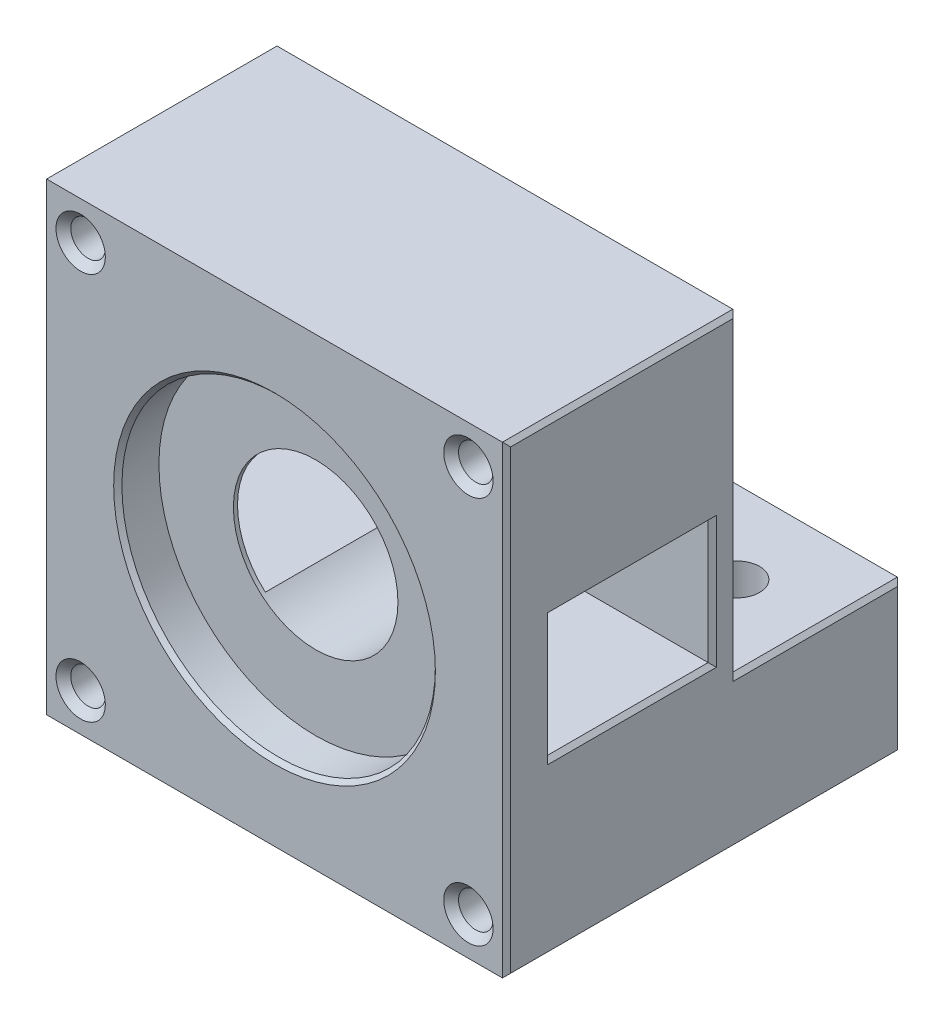
SolidWorks part; units mm, degrees
ref_plane "Front Plane" through (0, 0, 0) normal (0, 0, 1) x (1, 0, 0)
ref_plane "Top Plane" through (0, 0, 0) normal (0, 1, 0) x (1, 0, 0)
ref_plane "Right Plane" through (0, 0, 0) normal (1, 0, 0) x (0, 0, -1)
sketch "Sketch1" plane through (0, 0, 0) normal (0, 0, 1) x (1, 0, 0)
  line L1 (-28.2, 28.2) -> (28.2, 28.2)
  line L2 (-28.2, 28.2) -> (-28.2, -28.2)
  line L3 (-28.2, -28.2) -> (28.2, -28.2)
  line L4 (28.2, 28.2) -> (28.2, -28.2)
  line L5 (-28.2, 28.2) -> (28.2, -28.2) construction
  line L6 (-28.2, -28.2) -> (28.2, 28.2) construction
  point P0 (0, 0)
  dimension "D1" = 56.4
extrude "Boss-Extrude1" add sketch "Sketch1" along normal blind 28
sketch "Sketch2" plane through (0, 0, 0) normal (0, 0, -1) x (-1, 0, 0)
  line L0 (-28.2, -28.2) -> (-28.2, 28.2) construction
  line L1 (28.2, -28.2) -> (-28.2, -28.2)
  line L2 (28.2, -28.2) -> (28.2, -10)
  line L3 (28.2, -10) -> (-28.2, -10)
  line L4 (-28.2, -28.2) -> (-28.2, -10)
  dimension "D1" = 10
extrude "Boss-Extrude2" add sketch "Sketch2" along normal blind 20
sketch "Sketch3" plane through (0, -28.2, 0) normal (0, -1, 0) x (1, 0, 0)
  line L0 (-28.2, -10) -> (28.2, -10) construction
  line L1 (-28.2, 28) -> (-28.2, -20) construction
  line L2 (28.2, 28) -> (28.2, -20) construction
  line L3 (28.2, -20) -> (-28.2, -20) construction
  point P8 (-18.2, -10)
  point P9 (0, -10)
  point P10 (18.2, -10)
  dimension "D1" = 10
  dimension "D2" = 10
  dimension "D3" = 10
hole_wizard "CBORE for M5 SHCS1" positions "Sketch8" profile "Sketch7" counterbore size "M5" standard "ANSI Metric" end condition through all
sketch "Sketch8" plane through (0, -28.2, 0) normal (0, -1, 0) x (-1, 0, 0)
  point P0 (18.2, 10)
  point P3 (0, 10)
  point P6 (-18.2, 10)
sketch "Sketch7" plane through (-18.2, -28.2, -10) normal (1, 0, 0) x (0, 0, -1)
  line L0 (0, 0) -> (0, 56.4)
  line L1 (0, 56.4) -> (2.75, 56.4)
  line L3 (2.75, 56.4) -> (2.75, 13)
  line L4 (2.75, 13) -> (5, 13)
  line L5 (5, 13) -> (5, 0)
  line L7 (5, 0) -> (0, 0)
  line L11 (0, -6.35) -> (0, 107.95) construction
  dimension "Thru Hole Dia." = 5.5
  dimension "Thru Hole Depth" = 56.4
  dimension "C'Bore Dia." = 10
  dimension "C'Bore Depth" = 13
sketch "Sketch9" plane through (0, 0, 28) normal (0, 0, 1) x (1, 0, 0)
  circle A0 centre (0, 0) radius 19.05
  dimension "D1" = 38.1
extrude "Cut-Extrude1" cut sketch "Sketch9" against normal blind 5
chamfer "Chamfer1" distance 0.5 angle 45 1 edges at (19.05, 0, 28)
sketch "Sketch10" plane through (0, 0, 23) normal (0, 0, 1) x (1, 0, 0)
  circle A0 centre (0, 0) radius 10
  dimension "D1" = 20
extrude "Cut-Extrude2" cut sketch "Sketch10" against normal through all
sketch "Sketch11" plane through (-28.2, 0, 0) normal (-1, 0, 0) x (0, 0, 1)
  line L0 (0, 28.2) -> (0, -10) construction
  line L1 (22.5, 7.5) -> (3, 7.5)
  line L2 (22.5, 7.5) -> (22.5, -7.5)
  line L3 (22.5, -7.5) -> (3, -7.5)
  line L4 (3, 7.5) -> (3, -7.5)
  line L6 (0, 0) -> (3, 0) construction
  dimension "D1" = 3
  dimension "D2" = 19.5
  dimension "D3" = 15
extrude "Cut-Extrude3" cut sketch "Sketch11" against normal through all
sketch "Sketch12" plane through (0, 0, 28) normal (0, 0, 1) x (1, 0, 0)
  line L1 (23.565, 23.565) -> (-23.565, 23.565)
  line L2 (23.565, 23.565) -> (23.565, -23.565)
  line L3 (23.565, -23.565) -> (-23.565, -23.565)
  line L4 (-23.565, 23.565) -> (-23.565, -23.565)
  line L5 (23.565, 23.565) -> (-23.565, -23.565) construction
  line L6 (23.565, -23.565) -> (-23.565, 23.565) construction
  point P0 (0, 0)
  dimension "D1" = 47.13
hole_wizard "M5x0.8 Tapped Hole1" positions "Sketch13" profile "Sketch15" tap size "M5x0.8" standard "ANSI Metric" end condition through all
sketch "Sketch13" plane through (0, 0, 28) normal (0, 0, 1) x (1, 0, 0)
  point P0 (23.565, 23.565)
  point P3 (23.565, -23.565)
  point P6 (-23.565, -23.565)
  point P9 (-23.565, 23.565)
sketch "Sketch15" plane through (23.565, 23.565, 28) normal (1, 0, 0) x (0, -1, 0)
  line L0 (0, 0) -> (0, 48)
  line L1 (0, 48) -> (2.1, 48)
  line L2 (2.1, 48) -> (2.1, 0.9)
  line L3 (2.1, 0.9) -> (3, 0)
  line L5 (3, 0) -> (0, 0)
  line L6 (-2.1, 0.9) -> (-3, 0) construction
  line L11 (0, -6.35) -> (0, 107.95) construction
  dimension "Thru Tap Drill Dia." = 4.2
  dimension "Thru Tap Drill Depth" = 48
  dimension "Near C'Sink Dia." = 6
  dimension "Near C'Sink Angle" = 90
cosmetic thread "Hole Thread1" parameters "D2"=5
cosmetic thread "Hole Thread2" parameters "D2"=5
cosmetic thread "Hole Thread3" parameters "D2"=5
cosmetic thread "Hole Thread4" parameters "D2"=5
chamfer "Chamfer2" distance 0.5 angle 45 20 edges at (28.2, 0, 28) (28.2, 28.2, 14) (28.2, 9.1, 0) (28.2, -10, -10) (28.2, -19.1, -20) (28.2, -28.2, 4) (28.2, 0, 3) (28.2, 7.5, 12.75) (28.2, 0, 22.5) (28.2, -7.5, 12.75) (-28.2, 28.2, 14) (-28.2, 0, 28) (-28.2, -28.2, 4) (-28.2, -19.1, -20) (-28.2, -10, -10) (-28.2, 9.1, 0) (-28.2, 0, 3) (-28.2, -7.5, 12.75) (-28.2, 0, 22.5) (-28.2, 7.5, 12.75)
